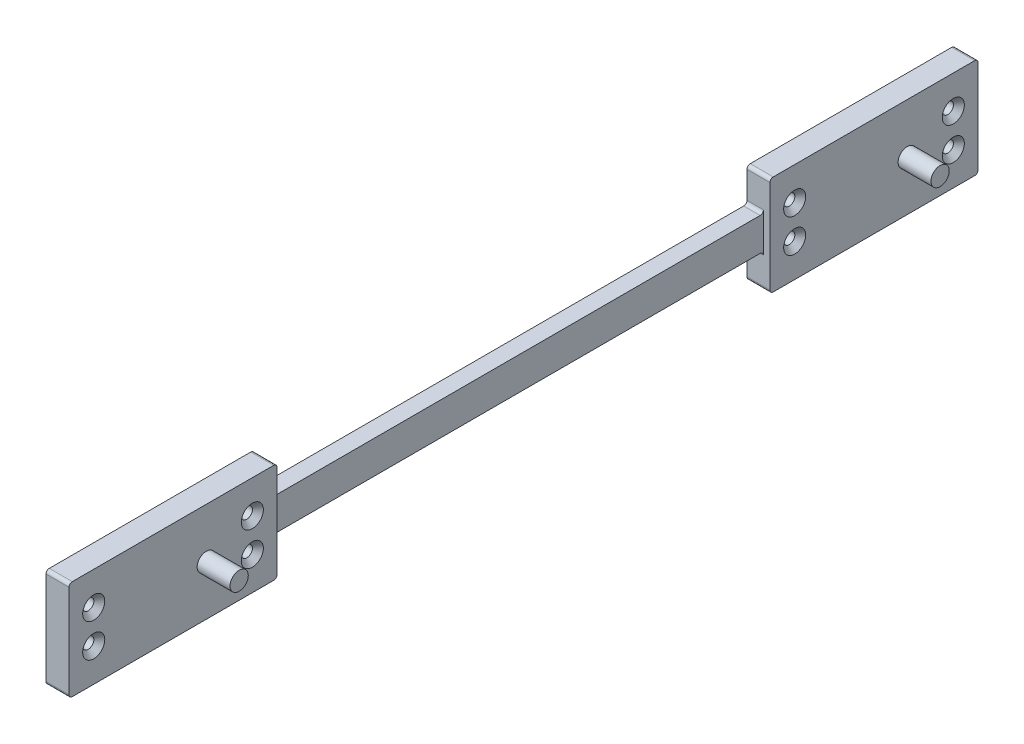
SolidWorks part; units mm, degrees
ref_plane "Front Plane" through (0, 0, 0) normal (0, 0, 1) x (1, 0, 0)
ref_plane "Top Plane" through (0, 0, 0) normal (0, 1, 0) x (1, 0, 0)
ref_plane "Right Plane" through (0, 0, 0) normal (1, 0, 0) x (0, 0, -1)
sketch "Sketch2" plane through (0, 0, 0) normal (1, 0, 0) x (0, 0, -1)
  line L0 (31.65, 5) -> (181.65, 5)
  line L1 (-31.65, 15.16) -> (31.65, 15.16)
  line L2 (-31.65, 15.16) -> (-31.65, -15.16)
  line L3 (-31.65, -15.16) -> (31.65, -15.16)
  line L4 (31.65, 15.16) -> (31.65, -15.16)
  line L5 (-31.65, 15.16) -> (31.65, -15.16) construction
  line L6 (-31.65, -15.16) -> (31.65, 15.16) construction
  line L7 (31.65, 5) -> (31.65, 0)
  line L8 (31.65, 0) -> (31.65, -5)
  line L9 (31.65, -5) -> (181.65, -5)
  line L10 (181.65, -5) -> (181.65, 0)
  line L11 (181.65, 0) -> (181.65, 5)
  line L12 (244.95, -15.16) -> (181.65, 15.16) construction
  line L13 (106.65, 65.8157) -> (106.65, -93.2692) construction
  line L14 (244.95, 15.16) -> (181.65, -15.16) construction
  line L15 (181.65, 0) -> (181.65, -5)
  line L16 (181.65, 5) -> (181.65, 0)
  line L17 (181.65, 15.16) -> (181.65, -15.16)
  line L18 (244.95, -15.16) -> (181.65, -15.16)
  line L19 (244.95, 15.16) -> (244.95, -15.16)
  line L20 (244.95, 15.16) -> (181.65, 15.16)
  point P0 (0, 0)
  point P18 (213.3, 0)
  dimension "D1" = 63.3
  dimension "D2" = 30.32
  dimension "D3" = 150
  dimension "D4" = 10
extrude "Boss-Extrude1" add sketch "Sketch2" along normal blind 5 contours L4 L1 L2 L3 | L10 L11 L0 L4 L9 | L19 L20 L17 L11 L10 L18 region at (0, 0, 0) region at (0, 0, -106.65) region at (0, 0, -213.3)
sketch "Sketch1" plane through (0, 0, 0) normal (1, 0, 0) x (0, 0, -1)
  line L1 (-20.32, 10.16) -> (20.32, 10.16)
  line L2 (-20.32, 10.16) -> (-20.32, -10.16)
  line L3 (-20.32, -10.16) -> (20.32, -10.16)
  line L4 (20.32, 10.16) -> (20.32, -10.16)
  line L5 (-20.32, 10.16) -> (20.32, -10.16) construction
  line L6 (-20.32, -10.16) -> (20.32, 10.16) construction
  line L7 (20.32, 3.16) -> (22.7, 3.16)
  line L8 (20.32, 3.16) -> (20.32, -3.19)
  line L9 (20.32, -3.19) -> (22.7, -3.19)
  line L10 (22.7, 3.16) -> (22.7, -3.19)
  point P0 (0, 0)
  dimension "D3" = 2.38
  dimension "D1" = 20.32
  dimension "D2" = 40.64
  dimension "D4" = 6.35
ref_axis "Axis1" through (0, 65.8157, -106.65) along (0, -1, 0)
extrude "Cut-Extrude3" cut sketch "Sketch1" along direction (1, 0, 0) on the side of the normal through all contours L4 L1 L2 L3 | L10 L7 L4 L9 region at (0, 0, 0) region at (0, -0.015, -21.51)
sketch "Sketch3" plane through (5, 0, 0) normal (1, 0, 0) x (0, 0, -1)
  line L0 (244.95, 15.16) -> (244.95, -15.16) construction
  line L1 (192.98, -10.16) -> (233.62, -10.16)
  line L2 (192.98, -10.16) -> (192.98, 10.16)
  line L3 (192.98, 10.16) -> (233.62, 10.16)
  line L4 (233.62, -10.16) -> (233.62, 10.16)
  line L5 (192.98, -10.16) -> (233.62, 10.16) construction
  line L6 (192.98, 10.16) -> (233.62, -10.16) construction
  line L10 (236, 3.175) -> (233.62, 3.175)
  line L11 (236, 3.175) -> (236, -3.175)
  line L12 (236, -3.175) -> (233.62, -3.175)
  line L13 (233.62, 3.175) -> (233.62, -3.175)
  line L14 (236, 3.175) -> (233.62, -3.175) construction
  line L15 (236, -3.175) -> (233.62, 3.175) construction
  point P0 (213.3, 0)
  point P8 (234.81, 0)
  dimension "D1" = 20.32
  dimension "D2" = 40.64
  dimension "D3" = 11.33
  dimension "D4" = 2.38
  dimension "D5" = 6.35
extrude "Cut-Extrude5" cut sketch "Sketch3" against normal through all contours L1 L4 L3 L2 | L12 L11 L10 L4 region at (5, 0, -213.3) region at (5, 0, -234.81)
sketch "Sketch7" plane through (5, 0, 0) normal (1, 0, 0) x (0, 0, -1)
  line L1 (-31.65, -15.16) -> (31.65, -15.16)
  line L2 (-31.65, -15.16) -> (-31.65, 15.16)
  line L3 (-31.65, 15.16) -> (31.65, 15.16)
  line L4 (31.65, -15.16) -> (31.65, 15.16)
  line L5 (-31.65, -15.16) -> (31.65, 15.16) construction
  line L6 (-31.65, 15.16) -> (31.65, -15.16) construction
  point P0 (0, 0)
extrude "Boss-Extrude2" add sketch "Sketch7" along normal blind 2
sketch "Sketch10" plane through (7, 0, 0) normal (1, 0, 0) x (0, 0, -1)
  line L0 (31.65, 15.16) -> (-31.65, 15.16) construction
  line L1 (31.65, -15.16) -> (31.65, 15.16) construction
  circle A0 centre (10.12, 0) radius 2.78
  dimension "D1" = 5.56
  dimension "D2" = 15.16
  dimension "D3" = 21.53
extrude "Boss-Extrude3" add sketch "Sketch10" along normal blind 10
sketch "Sketch11" plane through (5, 0, 0) normal (1, 0, 0) x (0, 0, -1)
  line L1 (181.65, 15.16) -> (244.95, 15.16)
  line L2 (181.65, 15.16) -> (181.65, -15.16)
  line L3 (181.65, -15.16) -> (244.95, -15.16)
  line L4 (244.95, 15.16) -> (244.95, -15.16)
extrude "Boss-Extrude4" add sketch "Sketch11" along normal blind 2
sketch "Sketch12" plane through (7, 0, 0) normal (1, 0, 0) x (0, 0, -1)
  line L0 (244.95, -15.16) -> (244.95, 15.16) construction
  line L1 (244.95, 15.16) -> (181.65, 15.16) construction
  circle A0 centre (223.42, 0) radius 2.78
  point P4 (213.3, 15.16)
  dimension "D1" = 5.56
  dimension "D2" = 21.53
  dimension "D3" = 15.16
extrude "Boss-Extrude5" add sketch "Sketch12" along normal blind 10
fillet "Fillet1" radius 1 12 edges at (3.5, -15.16, -244.95) (3.5, 15.16, -244.95) (3.5, 15.16, -181.65) (2.5, 5, -181.65) (3.5, -15.16, -181.65) (2.5, -5, -181.65) (3.5, 15.16, -31.65) (3.5, -15.16, -31.65) (3.5, -15.16, 31.65) (3.5, 15.16, 31.65)
hole_wizard "CSK for M3 SFHCS1" positions "Sketch14" profile "Sketch13" countersink size "M3" standard "ANSI Metric" end condition through all
sketch "Sketch14" plane through (7, 0, 0) normal (1, 0, 0) x (0, 0, -1)
  line L0 (-31.65, 14.16) -> (-31.65, -14.16) construction
  line L1 (30.65, 15.16) -> (-30.65, 15.16) construction
  line L2 (-30.65, -15.16) -> (30.65, -15.16) construction
  line L3 (31.65, -14.16) -> (31.65, 14.16) construction
  line L4 (181.65, 14.16) -> (181.65, -14.16) construction
  line L5 (244.95, -14.16) -> (244.95, 14.16) construction
  point P0 (-24.13, 5.08)
  point P2 (-24.13, -5.08)
  point P4 (24.13, -5.08)
  point P6 (24.13, 5.08)
  point P8 (189.17, 5.08)
  point P10 (189.17, -5.08)
  point P12 (237.43, 5.08)
  point P14 (237.43, -5.08)
  dimension "D1" = 7.52
  dimension "D2" = 10.08
  dimension "D3" = 10.08
  dimension "D4" = 7.52
  dimension "D5" = 7.52
  dimension "D6" = 7.52
sketch "Sketch13" plane through (7, 5.08, 24.13) normal (0, 1, 0) x (0, 0, -1)
  line L0 (0, 0) -> (0, 7)
  line L1 (0, 7) -> (1.7, 7)
  line L2 (1.7, 7) -> (1.7, 1.66)
  line L3 (1.7, 1.66) -> (3.36, 0)
  line L5 (3.36, 0) -> (0, 0)
  line L6 (-1.7, 1.66) -> (-3.36, 0) construction
  line L11 (0, -6.35) -> (0, 107.95) construction
  dimension "Thru Hole Dia." = 3.4
  dimension "Thru Hole Depth" = 7
  dimension "Near C'Sink Dia." = 6.72
  dimension "Near C'Sink Angle" = 90
